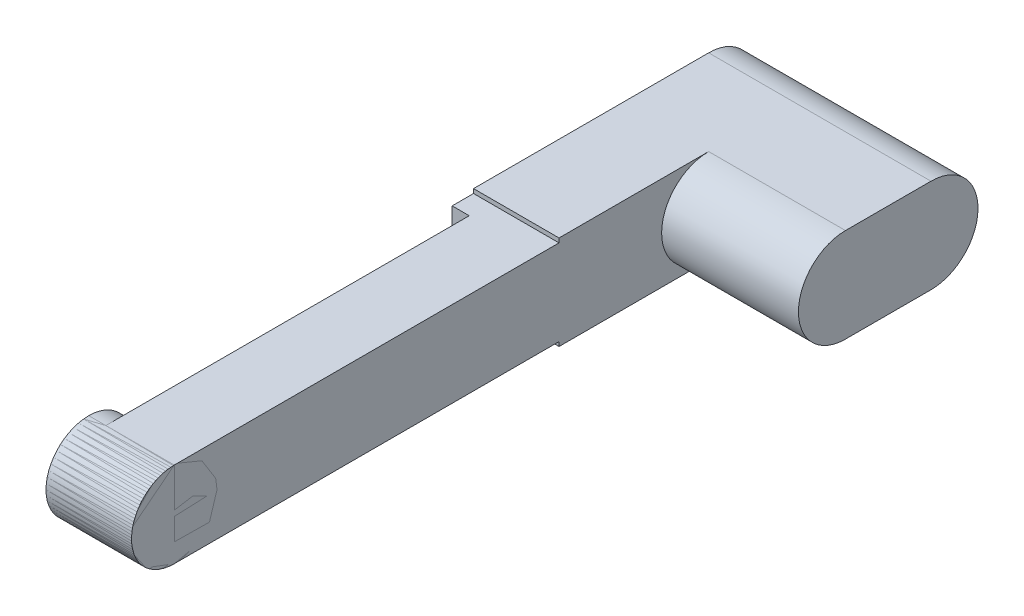
SolidWorks part; units mm, degrees
ref_plane "Front Plane" through (0, 0, 0) normal (0, 0, 1) x (1, 0, 0)
ref_plane "Top Plane" through (0, 0, 0) normal (0, 1, 0) x (1, 0, 0)
ref_plane "Right Plane" through (0, 0, 0) normal (1, 0, 0) x (0, 0, -1)
sketch "Sketch1" plane through (0, 0, 0) normal (1, 0, 0) x (0, 0, -1)
  line L0 (0, 0) -> (-500, 0) construction
  line L5 (-500, 50) -> (-50, 50)
  line L6 (50, -55) -> (-50, -55)
  line L7 (50, -55) -> (50, 55)
  line L8 (50, 55) -> (-50, 55)
  line L9 (-50, -55) -> (-50, 55)
  line L10 (50, -55) -> (-50, 55) construction
  line L11 (50, 55) -> (-50, -55) construction
  line L12 (-500, -50) -> (-50, -50)
  line L13 (0, 0) -> (280, 0)
  line L15 (280, 0) -> (50, 0)
  line L16 (280, 0) -> (280, 55)
  line L17 (280, 55) -> (50, 55)
  line L18 (50, 0) -> (50, 55)
  line L19 (280, 0) -> (50, 0)
  line L20 (280, 0) -> (280, -55)
  line L21 (280, -55) -> (50, -55)
  line L22 (50, 0) -> (50, -55)
  circle A0 centre (-500, 0) radius 50
  dimension "D1" = 100
  dimension "D2" = 110
  dimension "D3" = 100
  dimension "D4" = 500
  dimension "D5" = 280
extrude "Boss-Extrude1" add sketch "Sketch1" along normal blind 100 contours A0 L9 | A0 | L9 L6 L7 L8 | L21 L20 L13 L7 | L16 L17 L7 L13 region at (0, 0, 255.5167) region at (0, 0, 500) region at (0, 52.5, 48.5134) region at (0, 27.5, -165) region at (0, -27.5, -165)
sketch "Sketch2" plane through (0, 55, 0) normal (0, 1, 0) x (1, 0, 0)
  line L0 (0, 280) -> (260, 280)
  line L1 (260, 280) -> (260, 70)
  line L2 (260, 70) -> (100, 70)
  line L4 (0, 280) -> (0, -50)
  line L5 (0, -50) -> (100, -50)
  line L6 (100, -50) -> (100, 280)
  line L7 (100, 280) -> (0, 280)
  line L8 (0, 280) -> (0, -50)
  line L10 (100, -50) -> (100, 280)
  line L11 (100, 280) -> (0, 280)
  line L15 (0, -50) -> (100, -50)
  line M9 (100, -50) -> (100, 280)
  dimension "D2" = 260
  dimension "D3" = 210
  dimension "D1" = 0
extrude "Boss-Extrude2" add sketch "Sketch2" against normal up to surface (110 mm away) contours L2 L1 L0 M9 region at (180, 55, -175) up to face at (50, -55, -115)
sketch "Sketch3" plane through (260, 0, 0) normal (1, 0, 0) x (0, 0, -1)
  line L4 (70, -55) -> (280, -55)
  line L5 (280, -55) -> (280, 55)
  line L6 (280, 55) -> (70, 55)
  line L7 (70, 55) -> (70, -55)
  line L8 (70, -55) -> (280, -55)
  line L9 (280, -55) -> (280, 55)
  line L10 (280, 55) -> (70, 55)
  line L11 (70, 55) -> (70, -55)
  circle A0 centre (125, 0) radius 55
  circle A1 centre (225, 0) radius 55
  line M5 (70, -55) -> (280, -55)
  line M6 (280, -55) -> (280, 55)
  line M7 (280, 55) -> (70, 55)
  line M8 (70, 55) -> (70, -55)
  dimension "D1" = 0
extrude "Cut-Extrude1" cut sketch "Sketch3" against normal up to surface (260 mm away) contours A1 L9 M7 | A1 M5 M6 region at (260, -42.7148, -267.7148) region at (260, 42.7148, -267.7148) up to face at (0, 0, 86.25)
extrude "Cut-Extrude2" cut sketch "Sketch3<3>" against normal up to surface (160 mm away) contours A0 L10 M8 | A0 L11 M5 region at (260, -42.7148, -82.2852) region at (260, 42.7148, -82.2852) up to face at (100, 0, 138.75)
sketch "Sketch3<3>" plane through (260, 0, 0) normal (1, 0, 0) x (0, 0, -1) same geometry as "Sketch3"
sketch "Sketch5" plane through (0, 55, 0) normal (0, 1, 0) x (1, 0, 0)
  line L0 (0, 0) -> (0, -75)
  line L1 (0, -75) -> (20, -75)
  line L2 (20, -75) -> (20, -500)
  line L6 (100, -50) -> (100, 125)
  line L7 (100, 125) -> (260, 125)
  line L8 (260, 125) -> (260, 225)
  line L9 (260, 225) -> (0, 225)
  line L10 (0, 225) -> (0, -50)
  line L11 (0, -50) -> (100, -50)
  line L12 (100, -50) -> (100, 125)
  line L13 (100, 125) -> (260, 125)
  line L14 (260, 125) -> (260, 225)
  line L15 (260, 225) -> (0, 225)
  line L16 (0, 225) -> (0, -50)
  line L21 (0, -50) -> (100, -50)
  dimension "D2" = 75
  dimension "D3" = 20
  dimension "D1" = 0
extrude "Boss-Extrude3" add sketch "Sketch1<3>" along normal blind 100 separate body contours A0 region at (0, 0, 500)
sketch "Sketch1<3>" plane through (0, 0, 0) normal (1, 0, 0) x (0, 0, -1) same geometry as "Sketch1"
sketch "Sketch6" plane through (0, 50, 0) normal (0, 1, 0) x (1, 0, 0)
  line L0 (0, -50) -> (0, -75)
  line L1 (0, -75) -> (20, -75)
  line L2 (20, -75) -> (20, -500)
  line L4 (0, -50) -> (0, -500)
  line L5 (0, -500) -> (100, -500)
  line L6 (100, -500) -> (100, -50)
  line L7 (100, -50) -> (0, -50)
  line L8 (0, -50) -> (0, -500)
  line L9 (0, -500) -> (100, -500)
  line L10 (100, -500) -> (100, -50)
  line L11 (100, -50) -> (0, -50)
  line M7 (0, -50) -> (0, -500)
  line M8 (0, -500) -> (100, -500)
  dimension "D2" = 25
  dimension "D3" = 20
  dimension "D1" = 0
extrude "Cut-Extrude4" cut sketch "Sketch6" against normal blind 100 contours L2 L1 M7 M8 region at (10, 50, 287.5)
sketch "Sketch7" plane through (20, 0, 0) normal (-1, 0, 0) x (0, 0, 1)
  line L1 (500, -50) -> (500, 50)
  line L2 (500, -50) -> (500, 50)
  arc A1 (500, 50) -> (500, -50) centre (500, 0) ccw
  arc A2 (500, 50) -> (500, -50) centre (500, 0) ccw
  dimension "D1" = 0
extrude "Boss-Extrude4" add sketch "Sketch7" along normal up to surface (20 mm away) separate body up to face at (0, 0, 525)
